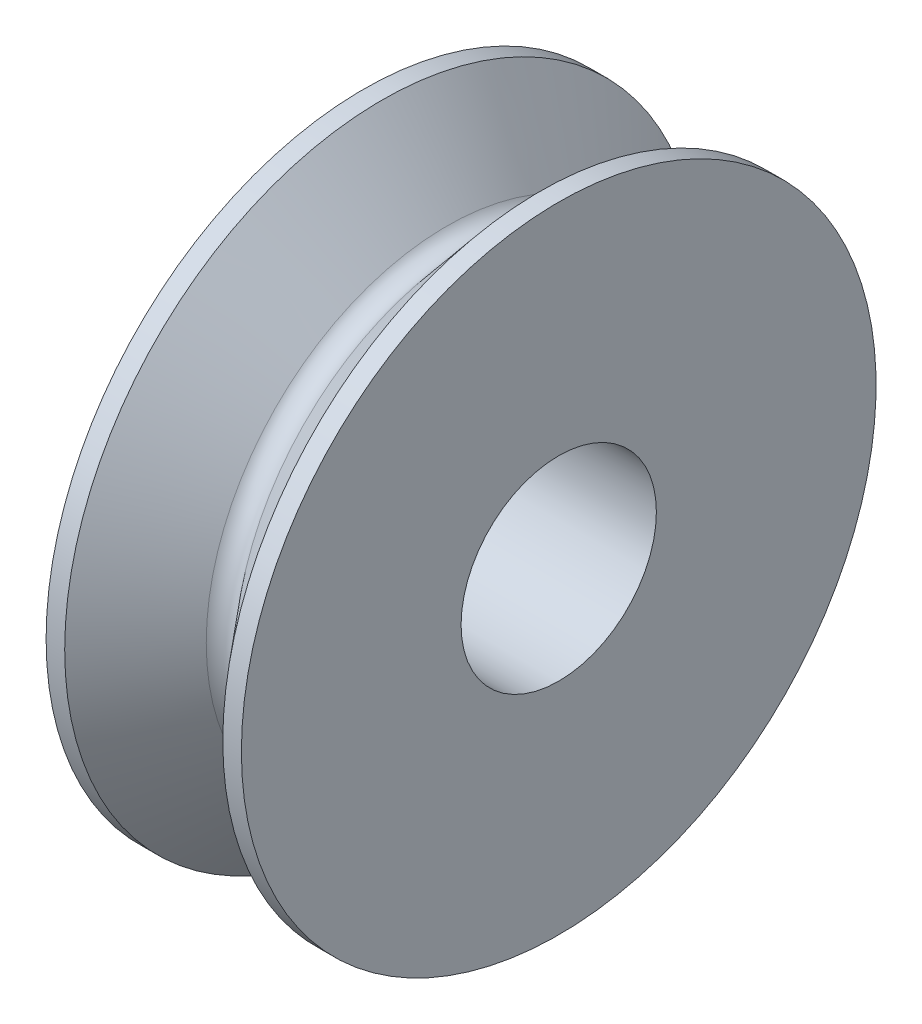
SolidWorks part; units mm, degrees
ref_plane "Front Plane" through (0, 0, 0) normal (0, 0, 1) x (1, 0, 0)
ref_plane "Top Plane" through (0, 0, 0) normal (0, 1, 0) x (1, 0, 0)
ref_plane "Right Plane" through (0, 0, 0) normal (1, 0, 0) x (0, 0, -1)
sketch "Sketch1" plane through (0, 0, 0) normal (0, 0, 1) x (1, 0, 0)
  line L0 (0, 0) -> (4, 0)
  line L1 (4, 0) -> (4, 4.5)
  line L2 (0, 4.5) -> (0, 0)
  line L3 (0, 0) -> (0, -2) construction
  line L4 (0, -2) -> (4, -2) construction
  line L5 (4, -2) -> (4, 0) construction
  line L6 (0, 4.5) -> (0.381, 4.5)
  line L7 (0.381, 4.5) -> (1.709, 2.929)
  line L8 (2.291, 2.929) -> (3.619, 4.5)
  line L9 (3.619, 4.5) -> (4, 4.5)
  arc A3 (1.709, 2.929) -> (2.291, 2.929) centre (2, 3.175) ccw
  point P8 (3.9456, 4.5847)
  point P10 (0, 4.5)
  point P14 (0, 0)
  point P15 (2.3545, 2.8956)
  dimension "D1" = 0.381
  dimension "D6" = 0.381
  dimension "D2" = 4
  dimension "D3" = 2
  dimension "D4" = 6.5
  dimension "D5" = 3.175
revolve "Revolve1" add sketch "Sketch1" angle 360 about L4
